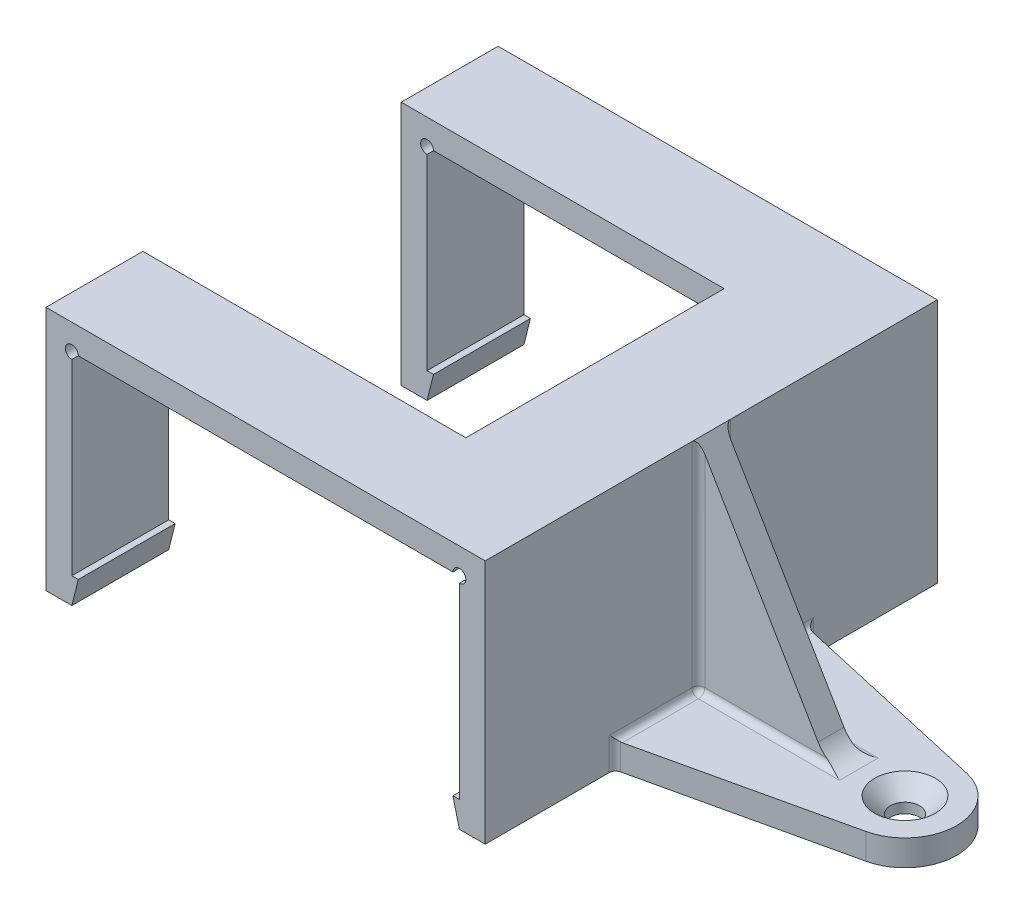
SolidWorks part; units mm, degrees
ref_plane "Plan de face" through (0, 0, 0) normal (0, 0, 1) x (1, 0, 0)
ref_plane "Plan de dessus" through (0, 0, 0) normal (0, 1, 0) x (1, 0, 0)
ref_plane "Plan de droite" through (0, 0, 0) normal (1, 0, 0) x (0, 0, -1)
sketch "Esquisse1" plane through (0, 0, 0) normal (0, 0, 1) x (1, 0, 0)
  line L0 (0, -38) -> (0, 0)
  line L1 (0, 0) -> (68, 0)
  line L2 (68, 0) -> (68, -38)
  line L3 (68, -38) -> (64, -38)
  line L4 (64, -38) -> (63, -34)
  line L5 (63, -34) -> (64, -34)
  line L6 (64, -34) -> (64, -5)
  line L7 (63, -4) -> (5, -4)
  line L8 (4, -5) -> (4, -34)
  line L9 (4, -34) -> (5, -34)
  line L10 (5, -34) -> (4, -38)
  line L11 (4, -38) -> (0, -38)
  arc A0 (64, -5) -> (63, -4) centre (64, -4) ccw
  arc A1 (5, -4) -> (4, -5) centre (4, -4) ccw
  dimension "D13" = 2
  dimension "D14" = 2
  dimension "D2" = 4
  dimension "D3" = 4
  dimension "D4" = 4
  dimension "D5" = 4
  dimension "D6" = 4
  dimension "D7" = 1
  dimension "D8" = 4
  dimension "D9" = 1
  dimension "D10" = 4
  dimension "D11" = 60
  dimension "D12" = 30
extrude "Forme principale" add sketch "Esquisse1" along normal mid plane 70
sketch "Esquisse3" plane through (0, 0, 0) normal (0, 1, 0) x (1, 0, 0)
  line L0 (50, 20) -> (0, 20)
  line L1 (50, 20) -> (50, -20)
  line L2 (0, 20) -> (0, -20)
  line L3 (50, -20) -> (0, -20)
  line L4 (50, 20) -> (0, -20) construction
  line L5 (0, 20) -> (50, -20) construction
  line L6 (0, -35) -> (0, 35) construction
  point P1 (25, 0)
  dimension "D1" = 40
  dimension "D2" = 50
extrude "Évidement" cut sketch "Esquisse3" against normal through all
sketch "Esquisse4" plane through (0, -38, 0) normal (0, -1, 0) x (1, 0, 0)
  line L0 (68, 15) -> (99.7678, 7.8022)
  line L1 (68, 35) -> (68, -35) construction
  line L2 (99.7678, -7.8022) -> (68, -15)
  line L3 (68, -15) -> (68, 15)
  arc A0 (99.7678, 7.8022) -> (99.7678, -7.8022) centre (98, 0) cw
  point P6 (68, 0)
  dimension "D2" = 8
  dimension "D1" = 30
  dimension "D3" = 30
extrude "Bossage écrou" add sketch "Esquisse4" against normal blind 4
hole_wizard "Fraisage pour vis à tête fraisée M41" positions "Esquisse8" profile "Esquisse7" countersink size "M4" standard "ISO" end condition through all
sketch "Esquisse8" plane through (0, -34, 0) normal (0, 1, 0) x (1, 0, 0)
  point P0 (98, 0)
  point P3 (98, 0)
sketch "Esquisse7" plane through (98, -34, 0) normal (1, 0, 0) x (0, 0, 1)
  line L0 (0, 0) -> (0, 4.0001)
  line L1 (0, 4.0001) -> (2.25, 4.0001)
  line L2 (2.25, 4.0001) -> (2.25, 2.45)
  line L3 (2.25, 2.45) -> (4.7, 0)
  line L5 (4.7, 0) -> (0, 0)
  line L6 (-2.25, 2.45) -> (-4.7, 0) construction
  line L11 (0, -6.35) -> (0, 107.95) construction
  dimension "Diamètre du perçage jusqu'au prochain" = 4.5
  dimension "Profondeur du perçage jusqu'au prochain" = 4.0001
  dimension "Diamètre du fraisage entrant" = 9.4
  dimension "Angle du fraisage entrant" = 90
sketch "Esquisse9" plane through (0, 0, 0) normal (0, 0, 1) x (1, 0, 0)
  line L0 (68, 0) -> (88, -34)
  line L3 (98, -34) -> (98, -38) construction
  dimension "D1" = 10
rib "Nervure3" sketch "Esquisse9" sketch "Esquisse9" thickness 4 extrusion direction parallel to sketch draft on no parameters "D1"=4
fillet "Congé2" radius 1 8 edges at (68, -34, -8.5) (78, -34, -2) (68, -17, -2) (78, -34, 2) (68, -34, 8.5) (68, -17, 2)
fillet "Congé3" radius 5 1 edges at (88, -34, 0)
